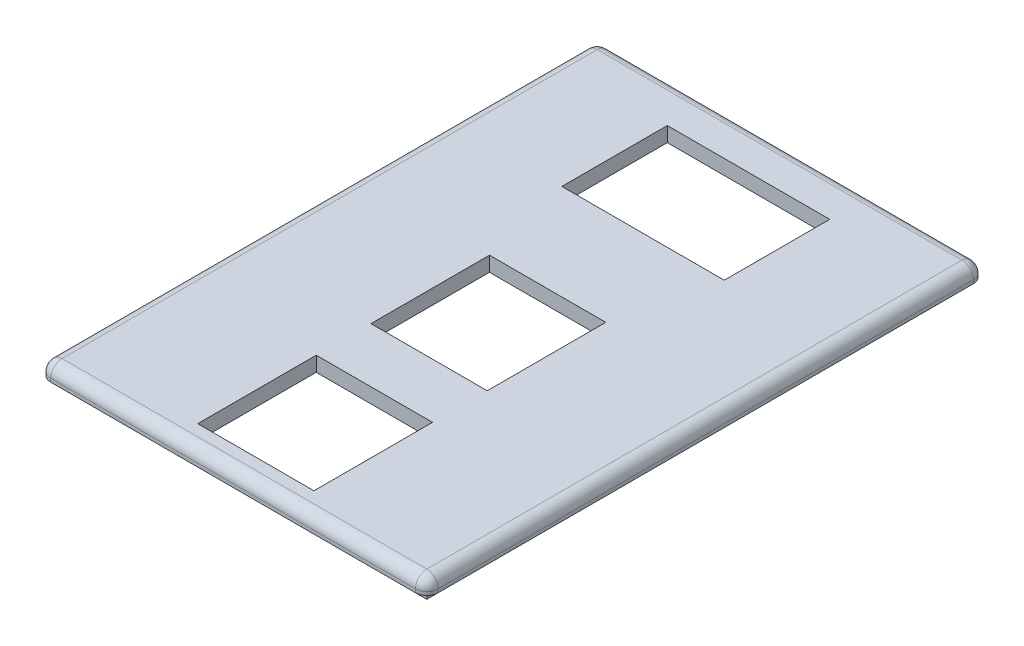
SolidWorks part; units mm, degrees
ref_plane "Front Plane" through (0, 0, 0) normal (0, 0, 1) x (1, 0, 0)
ref_plane "Top Plane" through (0, 0, 0) normal (0, 1, 0) x (1, 0, 0)
ref_plane "Right Plane" through (0, 0, 0) normal (1, 0, 0) x (0, 0, -1)
sketch "Sketch1" plane through (0, 0, 0) normal (0, 1, 0) x (1, 0, 0)
  line L1 (0, 0) -> (86.36, 0)
  line L2 (0, 0) -> (0, 124.333)
  line L3 (0, 124.333) -> (86.36, 124.333)
  line L4 (86.36, 0) -> (86.36, 124.333)
extrude "Boss-Extrude1" add sketch "Sketch1" along normal blind 3.302
sketch "Sketch2" plane through (0, 0, 0) normal (0, -1, 0) x (1, 0, 0)
  line L1 (2.54, -2.54) -> (83.82, -2.54)
  line L2 (2.54, -2.54) -> (2.54, -121.793)
  line L3 (2.54, -121.793) -> (83.82, -121.793)
  line L4 (83.82, -2.54) -> (83.82, -121.793)
extrude "Boss-Extrude2" add sketch "Sketch2" along normal blind 2.54
sketch "Sketch4" plane through (0, -2.54, 0) normal (0, -1, 0) x (1, 0, 0)
  line L2 (2.54, -121.793) -> (83.82, -121.793) construction
  line L3 (58.42, -121.793) -> (58.42, -119.253)
  line L4 (81.28, -119.253) -> (81.28, -5.08)
  line L5 (58.42, -119.253) -> (81.28, -119.253)
  line L6 (5.08, -119.253) -> (5.08, -5.08)
  line L7 (27.94, -121.793) -> (58.42, -121.793)
  line L8 (81.28, -5.08) -> (58.42, -5.08)
  line L9 (27.94, -2.54) -> (58.42, -2.54)
  line L10 (58.42, -5.08) -> (58.42, -2.54)
  line L11 (83.82, -2.54) -> (2.54, -2.54) construction
  line L12 (27.94, -2.54) -> (27.94, -5.08)
  line L13 (27.94, -5.08) -> (5.08, -5.08)
  line L14 (5.08, -119.253) -> (27.94, -119.253)
  line L15 (27.94, -119.253) -> (27.94, -121.793)
extrude "Cut-Extrude1" cut sketch "Sketch4" against normal blind 2.54
sketch "Sketch6" plane through (0, 3.302, 0) normal (0, 1, 0) x (1, 0, 0)
  line L1 (30.226, 5.08) -> (56.134, 5.08)
  line L2 (30.226, 5.08) -> (30.226, 31.496)
  line L3 (30.226, 31.496) -> (56.134, 31.496)
  line L4 (56.134, 5.08) -> (56.134, 31.496)
  line L5 (30.226, 43.688) -> (56.134, 43.688)
  line L6 (30.226, 43.688) -> (30.226, 70.104)
  line L7 (30.226, 70.104) -> (56.134, 70.104)
  line L8 (56.134, 43.688) -> (56.134, 70.104)
  line L9 (25.019, 114.935) -> (61.214, 114.935)
  line L10 (25.019, 114.935) -> (25.019, 91.44)
  line L11 (25.019, 91.44) -> (61.214, 91.44)
  line L12 (61.214, 114.935) -> (61.214, 91.44)
extrude "Cut-Extrude2" cut sketch "Sketch6" against normal blind 3.302
fillet "Fillet1" radius 2.54 8 edges at (86.36, 3.302, -62.1665) (43.18, 3.302, 0) (43.18, 3.302, -124.333) (0, 3.302, -62.1665) (0, 1.651, -124.333) (0, 1.651, 0) (86.36, 1.651, 0) (86.36, 1.651, -124.333)
